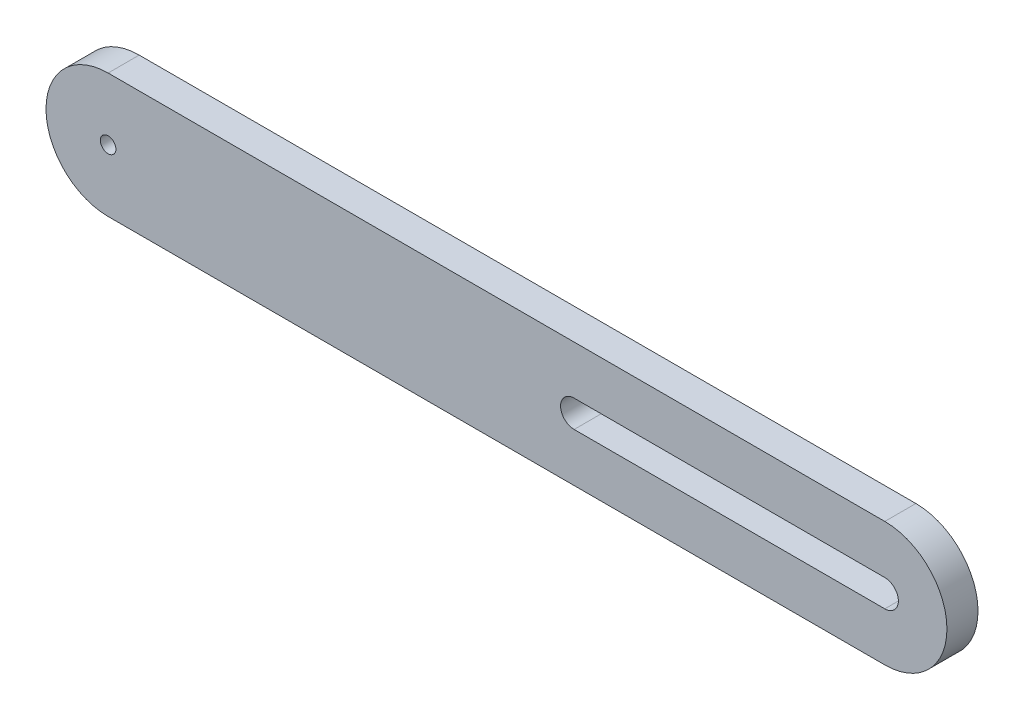
SolidWorks part; units mm, degrees
ref_plane "Front Plane" through (0, 0, 0) normal (0, 0, 1) x (1, 0, 0)
ref_plane "Top Plane" through (0, 0, 0) normal (0, 1, 0) x (1, 0, 0)
ref_plane "Right Plane" through (0, 0, 0) normal (1, 0, 0) x (0, 0, -1)
sketch "Sketch1" plane through (0, 0, 0) normal (0, 0, 1) x (1, 0, 0)
  line L0 (0, 0) -> (63.5, 0) construction
  line L1 (0, 5.08) -> (63.5, 5.08)
  line L2 (0, -5.08) -> (63.5, -5.08)
  arc A0 (0, 5.08) -> (0, -5.08) centre (0, 0) ccw
  arc A1 (63.5, -5.08) -> (63.5, 5.08) centre (63.5, 0) ccw
  point P3 (31.75, 0)
  dimension "D1" = 5.08
  dimension "D2" = 63.5
extrude "Boss-Extrude1" add sketch "Sketch1" along normal blind 2.54
sketch "Sketch2" plane through (0, 0, 2.54) normal (0, 0, 1) x (1, 0, 0)
  circle A0 centre (0, 0) radius 0.635
  dimension "D1" = 1.27
extrude "Cut-Extrude1" cut sketch "Sketch2" against normal through all both and the other way through all
ref_plane "Plane1" through (31.75, 0, 0) normal (1, 0, 0) x (0, 0, -1)
mirror "Mirror1" about plane through (31.75, 0, 0) normal (1, 0, 0) of "Cut-Extrude1"
sketch "Sketch4" plane through (0, 0, 2.54) normal (0, 0, 1) x (1, 0, 0)
  line L0 (63.5, 0) -> (38.0987, 0) construction
  line L1 (63.5, -1.108) -> (38.0987, -1.108)
  line L2 (63.5, 1.108) -> (38.0987, 1.108)
  arc A0 (63.5, -1.108) -> (63.5, 1.108) centre (63.5, 0) ccw
  arc A1 (38.0987, 1.108) -> (38.0987, -1.108) centre (38.0987, 0) ccw
  point P4 (50.7994, 0)
extrude "Cut-Extrude2" cut sketch "Sketch4" against normal through all both and the other way through all
